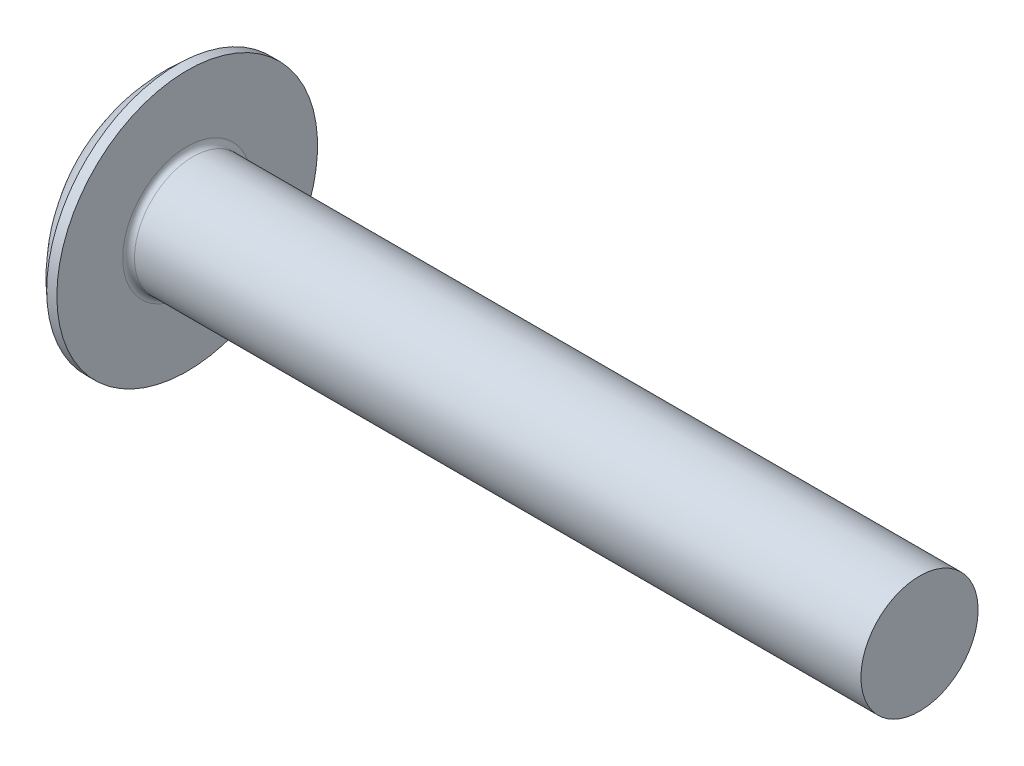
SolidWorks part; units mm, degrees
ref_plane "Front Plane" through (0, 0, 0) normal (0, 0, 1) x (1, 0, 0)
ref_plane "Top Plane" through (0, 0, 0) normal (0, 1, 0) x (1, 0, 0)
ref_plane "Right Plane" through (0, 0, 0) normal (1, 0, 0) x (0, 0, -1)
sketch "BodySke" plane through (0, 0, 0) normal (0, 0, 1) x (1, 0, 0)
  line L0 (0, 0) -> (111.3824, 0) construction
  line L1 (0, 0) -> (0, 8) construction
  line L2 (4.8, 4) -> (4.8, 8.9)
  line L3 (4.8, 8.9) -> (4.1053, 8.9)
  line L4 (4.8, 4) -> (54.8, 4)
  line L5 (54.8, 4) -> (54.8, 0)
  line L6 (6.05, 7.824) -> (6.05, -6.8939) construction
  line L7 (0, 0) -> (54.8, 0)
  line L8 (24.8, 8.824) -> (24.8, -4.958) construction
  arc A0 (0, 0) -> (4.1053, 8.9) centre (11.7, 0) cw
  point P10 (54.8, 3.4455)
  dimension "Thread_minor" = 6.891
  dimension "Head_height" = 4.8
  dimension "Advance" = 1.25
  dimension "Head_dia" = 17.8
  dimension "Length" = 50
revolve "BaseBody" add sketch "BodySke" angle 360 about L0
cosmetic thread "ThreadCosmetic" [suppressed] parameters "Thread_minor"=6.891
fillet "Fillet1" radius 0.4 1 edges at (4.8, 0, 4)
ref_plane "Plane1" through (4.36, 0, 0) normal (1, 0, 0) x (0, 0, -1)
sketch "RecSkeTop" plane through (0, 0, 0) normal (1, 0, 0) x (0, 0, -1)
  line L1 (-0.858, 3.9) -> (0.858, 3.9)
  line L2 (-0.858, 3.9) -> (-0.858, -3.9)
  line L3 (-0.858, -3.9) -> (0.858, -3.9)
  line L4 (0.858, 3.9) -> (0.858, -3.9)
  dimension "D1" = 3.9
  dimension "D2" = 1.716
  dimension "D3" = 0.858
sketch "RecSkeBot" plane through (4.36, 0, 0) normal (1, 0, 0) x (0, 0, -1)
  line L0 (-0.858, 3.9) -> (-0.858, -3.9) construction
  line L1 (-0.858, 1.7262) -> (0.858, 1.7262)
  line L2 (-0.858, 1.7262) -> (-0.858, -1.7262)
  line L3 (-0.858, -1.7262) -> (0.858, -1.7262)
  line L4 (0.858, 1.7262) -> (0.858, -1.7262)
  line L5 (0.858, 3.9) -> (0.858, -3.9) construction
  dimension "D1" = 3.4524
  dimension "D2" = 1.7262
loft "Recess" cut profiles "RecSkeTop", "RecSkeBot" connector at (0, -3.9, 0.858) connector at (4.36, -1.7262, 0.858)
pattern_circular "RecPat" count 2 every 90 about axis through (0, 0, 0) along (1, 0, 0) of "Recess"
sketch "RecCorSke" plane through (0, 0, 0) normal (0, 0, 1) x (1, 0, 0)
  line L0 (0, 0) -> (57.5987, 0) construction
  line L1 (0, 0) -> (0, 1.8876)
  line L3 (0, 1.8876) -> (4.36, 1.5827)
  line L4 (4.36, 1.5827) -> (4.8743, 0)
  line L5 (4.8743, 0) -> (0, 0)
  dimension "D1" = 18
  dimension "D2" = 4.36
  dimension "D3" = 1.8876
  dimension "D4" = 4
revolve "RecessCore" cut sketch "RecCorSke" angle 360 about L0
sketch "ThdSchSke" plane through (0, 0, 0) normal (0, 0, 1) x (1, 0, 0)
  line L0 (0, 0) -> (55.1256, 0) construction
  line L1 (0, 0) -> (111.3824, 0) construction
  line L2 (54.4799, 4) -> (54.4799, 4.6403)
  line L3 (54.4799, 4.6403) -> (55.1201, 4.6403)
  line L4 (55.1201, 4.6403) -> (55.1201, 4)
  line L5 (55.1201, 4) -> (54.8, 3.4455)
  line L6 (54.8, 3.4455) -> (54.4799, 4)
  line L7 (4.8, 4) -> (54.8, 4) construction
  line L13 (54.8, 4) -> (54.8, 0) construction
revolve "ThreadSchematic" [suppressed] cut sketch "ThdSchSke" angle 360 about L0
pattern_linear "ThdSchPat" [suppressed] count 24 along (-1, 0, 0) of bodies 103
equation "\"Thread_minor@ThreadCosmetic\" = \"Thread_minor@BodySke\""
equation "\"D1@RecSkeTop\" = \"Cross_dia@RecSkeTop\" / 2"
equation "\"D2@RecSkeTop\" = \"Cross_dia@RecSkeTop\" * 0.22"
equation "\"D3@RecSkeTop\" = \"D2@RecSkeTop\" / 2"
equation "\"D1@RecSkeBot\" = \"Cross_dia@RecSkeTop\" - 2 * \"Cross_depth@Plane1\" *  tan( 26.5 * 0.017453292 ) "
equation "\"D2@RecSkeBot\" = \"D1@RecSkeBot\" / 2"
equation "\"D2@RecCorSke\" = \"Cross_depth@Plane1\""
equation "\"D3@RecCorSke\" = \"D2@RecSkeTop\" * 1.1"
equation "\"Advance@ThdSchPat\" = \"Advance@BodySke\""
equation "\"D1@ThdSchPat\" =  int( \"Thread_length@BodySke\" / \"Advance@ThdSchPat\" ) "
